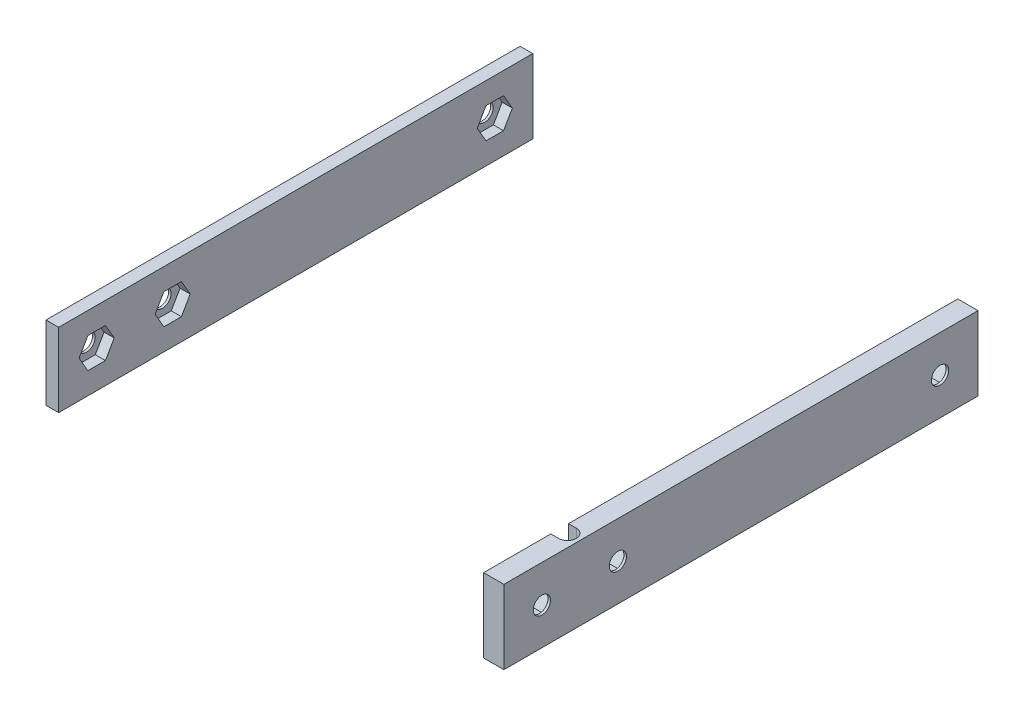
SolidWorks part; units mm, degrees
ref_plane "Front Plane" through (0, 0, 0) normal (0, 0, 1) x (1, 0, 0)
ref_plane "Top Plane" through (0, 0, 0) normal (0, 1, 0) x (1, 0, 0)
ref_plane "Right Plane" through (0, 0, 0) normal (1, 0, 0) x (0, 0, -1)
sketch "Sketch1" plane through (0, 0, 0) normal (0, 1, 0) x (1, 0, 0)
  line L1 (-45.2, -46.8) -> (45.2, -46.8)
  line L2 (-45.2, -46.8) -> (-45.2, 46.8)
  line L3 (-45.2, 46.8) -> (45.2, 46.8)
  line L4 (45.2, -46.8) -> (45.2, 46.8)
  line L5 (-45.2, -46.8) -> (45.2, 46.8) construction
  line L6 (-45.2, 46.8) -> (45.2, -46.8) construction
  line L7 (-45.2, -46.8) -> (-42.7, -46.8)
  line L8 (-45.2, -46.8) -> (-45.2, 46.8)
  line L9 (-45.2, 46.8) -> (-42.7, 46.8)
  line L10 (-42.7, -46.8) -> (-42.7, 46.8)
  line L11 (-45.2, -46.8) -> (-42.7, 46.8) construction
  line L12 (-45.2, 46.8) -> (-42.7, -46.8) construction
  line L13 (45.2, -46.8) -> (41.2, -46.8)
  line L14 (45.2, -46.8) -> (45.2, 46.8)
  line L15 (45.2, 46.8) -> (41.2, 46.8)
  line L16 (41.2, -46.8) -> (41.2, 46.8)
  line L17 (45.2, -46.8) -> (41.2, 46.8) construction
  line L18 (45.2, 46.8) -> (41.2, -46.8) construction
  point P0 (0, 0)
  point P6 (-43.95, 0)
  point P11 (43.2, 0)
  dimension "D1" = 93.6
  dimension "D2" = 90.4
  dimension "D3" = 2.5
  dimension "D4" = 4
extrude "Boss-Extrude1" add sketch "Sketch1" along normal blind 14.6 contours L1 L10 L3 L2 | L16 L1 L4 L3 region at (-43.95, 0, 0) region at (43.2, 0, 0)
sketch "Sketch4" plane through (0, 14.6, 0) normal (0, 1, 0) x (1, 0, 0)
  line L0 (41.2, -46.8) -> (45.2, -46.8) construction
  line L1 (45.2, -46.8) -> (45.2, 46.8) construction
  line L2 (42.75, -31.8) -> (42.75, -30.05)
  line L3 (42.75, -30.05) -> (41.2, -30.05)
  line L4 (41.2, -46.8) -> (41.2, 46.8) construction
  line L5 (42.75, -31.8) -> (42.75, -33.55)
  line L6 (42.75, -33.55) -> (41.2, -33.55)
  line L7 (41.2, -33.55) -> (41.2, -30.05)
  circle A0 centre (42.75, -31.8) radius 1.75
  line M2 (41.2, 46.8) -> (41.2, -46.8)
  dimension "D3" = 3.5
  dimension "D1" = 15
  dimension "D2" = 2.45
extrude "Cut-Extrude1" cut sketch "Sketch4" against normal through all contours L5 A0 L2 | L2 A0 L7 L5 | A0 L6 M2 | A0 L3 M2 region at (42.0497, 14.6, 31.8) region at (43.4927, 14.6, 31.8) region at (41.5638, 14.6, 30.3111) region at (41.5638, 14.6, 33.2889)
hole_wizard "M3 Clearance Hole1" positions "Sketch6" profile "Sketch7" hole size "M3" standard "ANSI Metric" end condition through all
sketch "Sketch6" plane through (45.2, 0, 0) normal (1, 0, 0) x (0, 0, -1)
  line L0 (-46.8, 7.3) -> (46.8, 7.3)
  line L1 (-46.8, 14.6) -> (-46.8, 0) construction
  line L2 (46.8, 14.6) -> (46.8, 0) construction
  point P8 (-39.3, 7.3)
  point P10 (39.3, 7.3)
  point P12 (-24.3, 7.3)
  dimension "D1" = 7.5
  dimension "D2" = 7.5
  dimension "D3" = 22.5
sketch "Sketch7" plane through (45.2, 7.3, 24.3) normal (0, 1, 0) x (0, 0, -1)
  line L0 (0, 0) -> (0, 90.4)
  line L1 (0, 90.4) -> (1.7, 90.4)
  line L2 (1.7, 90.4) -> (1.7, 0)
  line L5 (1.7, 0) -> (0, 0)
  line L11 (0, -6.35) -> (0, 107.95) construction
  dimension "Thru Hole Dia." = 3.4
  dimension "Thru Hole Depth" = 90.4
sketch "Sketch8" plane through (41.2, 0, 0) normal (-1, 0, 0) x (0, 0, 1)
  line L1 (-35.8359, 7.3) -> (-37.5679, 10.3)
  line L2 (-37.5679, 10.3) -> (-41.0321, 10.3)
  line L3 (-41.0321, 10.3) -> (-42.7641, 7.3)
  line L4 (-42.7641, 7.3) -> (-41.0321, 4.3)
  line L5 (-41.0321, 4.3) -> (-37.5679, 4.3)
  line L6 (-37.5679, 4.3) -> (-35.8359, 7.3)
  line L7 (27.7641, 7.3) -> (26.0321, 10.3)
  line L8 (26.0321, 10.3) -> (22.5679, 10.3)
  line L9 (22.5679, 10.3) -> (20.8359, 7.3)
  line L10 (20.8359, 7.3) -> (22.5679, 4.3)
  line L11 (22.5679, 4.3) -> (26.0321, 4.3)
  line L12 (26.0321, 4.3) -> (27.7641, 7.3)
  line L13 (42.7641, 7.3) -> (41.0321, 10.3)
  line L14 (41.0321, 10.3) -> (37.5679, 10.3)
  line L15 (37.5679, 10.3) -> (35.8359, 7.3)
  line L16 (35.8359, 7.3) -> (37.5679, 4.3)
  line L17 (37.5679, 4.3) -> (41.0321, 4.3)
  line L18 (41.0321, 4.3) -> (42.7641, 7.3)
  circle A0 centre (-39.3, 7.3) radius 3.4641 construction
  circle A1 centre (24.3, 7.3) radius 3.4641 construction
  circle A2 centre (39.3, 7.3) radius 3 construction
  dimension "D1" = 3
extrude "Cut-Extrude2" cut sketch "Sketch8" against normal blind 3.5
mirror "Mirror1" about plane through (0, 0, 0) normal (1, 0, 0) of "Cut-Extrude2"
sketch "Sketch10" [suppressed] plane through (0, 14.6, 0) normal (0, 1, 0) x (1, 0, 0)
  line L0 (42.75, -33.55) -> (41.2, -33.55) construction
  line L1 (41.2, -33.55) -> (41.2, -46.8) construction
  line L2 (41.2, -46.8) -> (45.2, -46.8) construction
  line L3 (45.2, -46.8) -> (45.2, 46.8) construction
  line L4 (45.2, 46.8) -> (41.2, 46.8) construction
  line L5 (41.2, 46.8) -> (41.2, -30.05) construction
  line L6 (41.2, -30.05) -> (42.75, -30.05) construction
  line L7 (-45.2, -46.8) -> (-42.7, -46.8) construction
  line L8 (-42.7, -46.8) -> (-42.7, 46.8) construction
  line L9 (-42.7, 46.8) -> (-45.2, 46.8) construction
  line L10 (-45.2, 46.8) -> (-45.2, -46.8) construction
  line L11 (42.75, -33.55) -> (41.2, -33.55)
  line L12 (41.2, -33.55) -> (41.2, -46.8)
  line L13 (41.2, -46.8) -> (45.2, -46.8)
  line L14 (45.2, -46.8) -> (45.2, 46.8)
  line L15 (45.2, 46.8) -> (41.2, 46.8)
  line L16 (41.2, 46.8) -> (41.2, -30.05)
  line L17 (41.2, -30.05) -> (42.75, -30.05)
  line L18 (-45.2, -46.8) -> (-42.7, -46.8)
  line L19 (-42.7, -46.8) -> (-42.7, 46.8)
  line L20 (-42.7, 46.8) -> (-45.2, 46.8)
  line L21 (-45.2, 46.8) -> (-45.2, -46.8)
  arc A0 (42.75, -33.55) -> (42.75, -30.05) centre (42.75, -31.8) ccw construction
  arc A1 (42.75, -33.55) -> (42.75, -30.05) centre (42.75, -31.8) ccw
extrude "Boss-Extrude2" [suppressed] add sketch "Sketch10" along normal blind 7.5
sketch "Sketch11" [suppressed] plane through (0, 0, 0) normal (0, -1, 0) x (1, 0, 0)
  line L0 (-42.7, 46.8) -> (-45.2, 46.8) construction
  line L1 (-45.2, 46.8) -> (-45.2, -46.8) construction
  line L2 (-45.2, -46.8) -> (-42.7, -46.8) construction
  line L3 (-42.7, -46.8) -> (-42.7, 46.8) construction
  line L4 (41.2, 33.55) -> (42.75, 33.55) construction
  line L5 (42.75, 30.05) -> (41.2, 30.05) construction
  line L6 (41.2, 30.05) -> (41.2, -46.8) construction
  line L7 (41.2, -46.8) -> (45.2, -46.8) construction
  line L8 (45.2, -46.8) -> (45.2, 46.8) construction
  line L9 (45.2, 46.8) -> (41.2, 46.8) construction
  line L10 (41.2, 46.8) -> (41.2, 33.55) construction
  line L11 (-42.7, 46.8) -> (-45.2, 46.8)
  line L12 (-45.2, 46.8) -> (-45.2, -46.8)
  line L13 (-45.2, -46.8) -> (-42.7, -46.8)
  line L14 (-42.7, -46.8) -> (-42.7, 46.8)
  line L15 (41.2, 33.55) -> (42.75, 33.55)
  line L16 (42.75, 30.05) -> (41.2, 30.05)
  line L17 (41.2, 30.05) -> (41.2, -46.8)
  line L18 (41.2, -46.8) -> (45.2, -46.8)
  line L19 (45.2, -46.8) -> (45.2, 46.8)
  line L20 (45.2, 46.8) -> (41.2, 46.8)
  line L21 (41.2, 46.8) -> (41.2, 33.55)
  arc A0 (42.75, 30.05) -> (42.75, 33.55) centre (42.75, 31.8) ccw construction
  arc A1 (42.75, 30.05) -> (42.75, 33.55) centre (42.75, 31.8) ccw
extrude "Boss-Extrude3" [suppressed] add sketch "Sketch11" along normal blind 7.5
